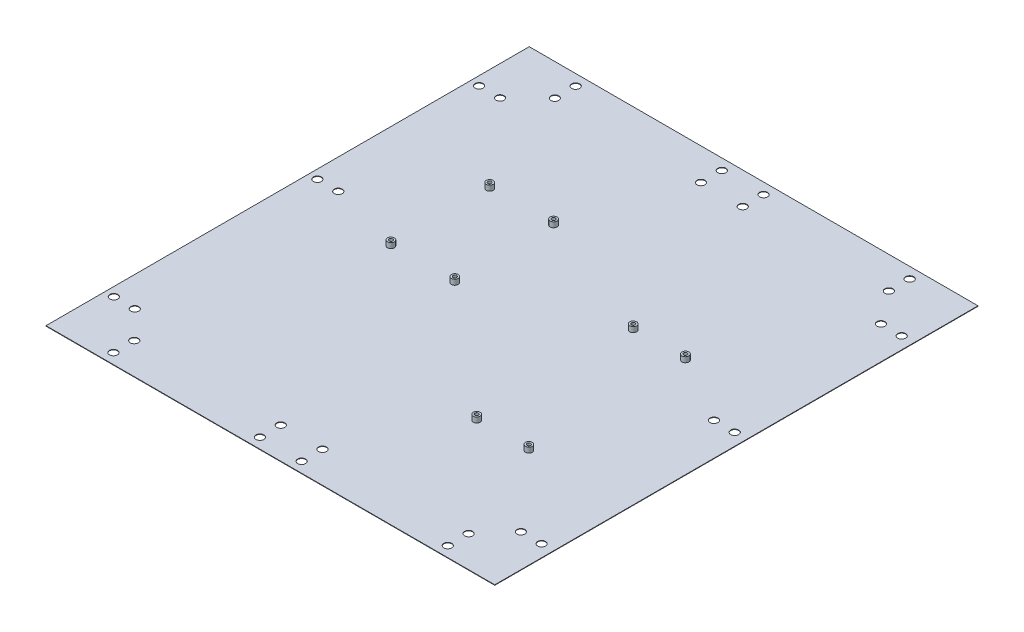
SolidWorks part; units mm, degrees
ref_plane "Front Plane" through (0, 0, 0) normal (0, 0, 1) x (1, 0, 0)
ref_plane "Top Plane" through (0, 0, 0) normal (0, 1, 0) x (1, 0, 0)
ref_plane "Right Plane" through (0, 0, 0) normal (1, 0, 0) x (0, 0, -1)
sketch "Sketch1" plane through (0, 0, 0) normal (0, 1, 0) x (1, 0, 0)
  line L1 (-215, -231.5) -> (215, -231.5)
  line L2 (-215, -231.5) -> (-215, 231.5)
  line L3 (-215, 231.5) -> (215, 231.5)
  line L4 (215, -231.5) -> (215, 231.5)
  line L5 (-215, -231.5) -> (215, 231.5) construction
  line L6 (-215, 231.5) -> (215, -231.5) construction
  point P0 (0, 0)
  dimension "D1" = 430
  dimension "D2" = 463
extrude "Boss-Extrude1" add sketch "Sketch1" along normal blind 0.45
sketch "Sketch6" plane through (0, 0.45, 0) normal (0, 1, 0) x (1, 0, 0)
  circle A0 centre (119.7933, 46.3731) radius 3.3
  circle A1 centre (69.7933, 46.3731) radius 3.3
  circle A2 centre (119.7933, -103.6269) radius 3.3
  circle A3 centre (69.7933, -103.6269) radius 3.3
sketch "Sketch7" plane through (0, 0.45, 0) normal (0, 1, 0) x (1, 0, 0)
  circle A0 centre (-116.3627, 94.9459) radius 3.3
  circle A1 centre (-55.3632, 95.1916) radius 3.3
  circle A2 centre (-54.9804, 0.1924) radius 3.3
  circle A3 centre (-115.98, -0.0534) radius 3.3
extrude "Boss-Extrude2" add sketch "Sketch7" along normal blind 5
sketch "Sketch8" plane through (0, 5.45, 0) normal (0, 1, 0) x (1, 0, 0)
  circle A0 centre (-54.9804, 0.1924) radius 1.75
  circle A1 centre (-55.3632, 95.1916) radius 1.75
  circle A2 centre (-116.3627, 94.9459) radius 1.75
  circle A3 centre (-115.98, -0.0534) radius 1.75
extrude "Cut-Extrude1" cut sketch "Sketch8" against normal blind 4
extrude "Boss-Extrude3" add sketch "Sketch6" along normal blind 5
sketch "Sketch10" plane through (0, 5.45, 0) normal (0, 1, 0) x (1, 0, 0)
  circle A0 centre (69.7933, 46.3731) radius 1.75
  circle A1 centre (119.7933, 46.3731) radius 1.75
  circle A2 centre (119.7933, -103.6269) radius 1.75
  circle A3 centre (69.7933, -103.6269) radius 1.75
extrude "Cut-Extrude2" cut sketch "Sketch10" against normal blind 4
sketch "Sketch12" plane through (0, 0, 0) normal (0, -1, 0) x (-1, 0, 0)
  circle A0 centre (-183.5287, -175) radius 3.8
  circle A1 centre (-203.3989, 170) radius 3.8
  circle A3 centre (-183.5287, 10) radius 3.8
  circle A4 centre (-203.3989, 10) radius 3.8
  circle A5 centre (-203.3989, -175) radius 3.8
  circle A6 centre (-183.5287, 170) radius 3.8
  circle A7 centre (206.5253, -175) radius 3.8
  circle A8 centre (206.5253, 20) radius 3.8
  circle A9 centre (186.4469, 175) radius 3.8
  circle A10 centre (206.5253, 175) radius 3.8
  circle A11 centre (186.4469, -175) radius 3.8
  circle A12 centre (186.4469, 20) radius 3.8
  circle A13 centre (160.3499, -221.5206) radius 3.8
  circle A14 centre (160.3499, -201.5484) radius 3.8
  circle A15 centre (20, -221.5206) radius 3.8
  circle A16 centre (20, -201.5484) radius 3.8
  circle A17 centre (-20, -201.5484) radius 3.8
  circle A19 centre (-20, -221.5206) radius 3.8
  circle A20 centre (-160, -221.5206) radius 3.8
  circle A21 centre (-160, -201.5484) radius 3.8
  circle A22 centre (160, 201.0677) radius 3.8
  circle A23 centre (160, 221.0364) radius 3.8
  circle A24 centre (20, 201.0677) radius 3.8
  circle A25 centre (20, 221.0364) radius 3.8
  circle A26 centre (-20, 201.0677) radius 3.8
  circle A27 centre (-20, 221.0364) radius 3.8
  circle A28 centre (-160, 201.0677) radius 3.8
  circle A29 centre (-160, 221.0364) radius 3.8
  point P54 (0, 0)
  point P55 (0, 0)
  point P58 (0, 0)
  point P59 (0, 0)
  point P60 (0, 0)
  point P61 (0, 0)
  point P62 (0, 0)
  point P63 (20, -221.7857)
  point P64 (20, -221.5206)
  point P65 (20, -202.304)
  point P66 (20, -201.5484)
  point P67 (0, 0)
  point P68 (0, 0)
  point P69 (0, 0)
  point P70 (0, 0)
  point P71 (0, 0)
  point P72 (0, 0)
  point P73 (0, 0)
  point P74 (160.3499, -221.5206)
  point P75 (-160, 221.0364)
  point P76 (-160, 201.0677)
  point P77 (0, 0)
  point P78 (0, 0)
  point P79 (0, 0)
  point P80 (0, 0)
  point P81 (0, 0)
  point P82 (0, 0)
  point P83 (0, 0)
extrude "Cut-Extrude3" cut sketch "Sketch12" against normal blind 10
